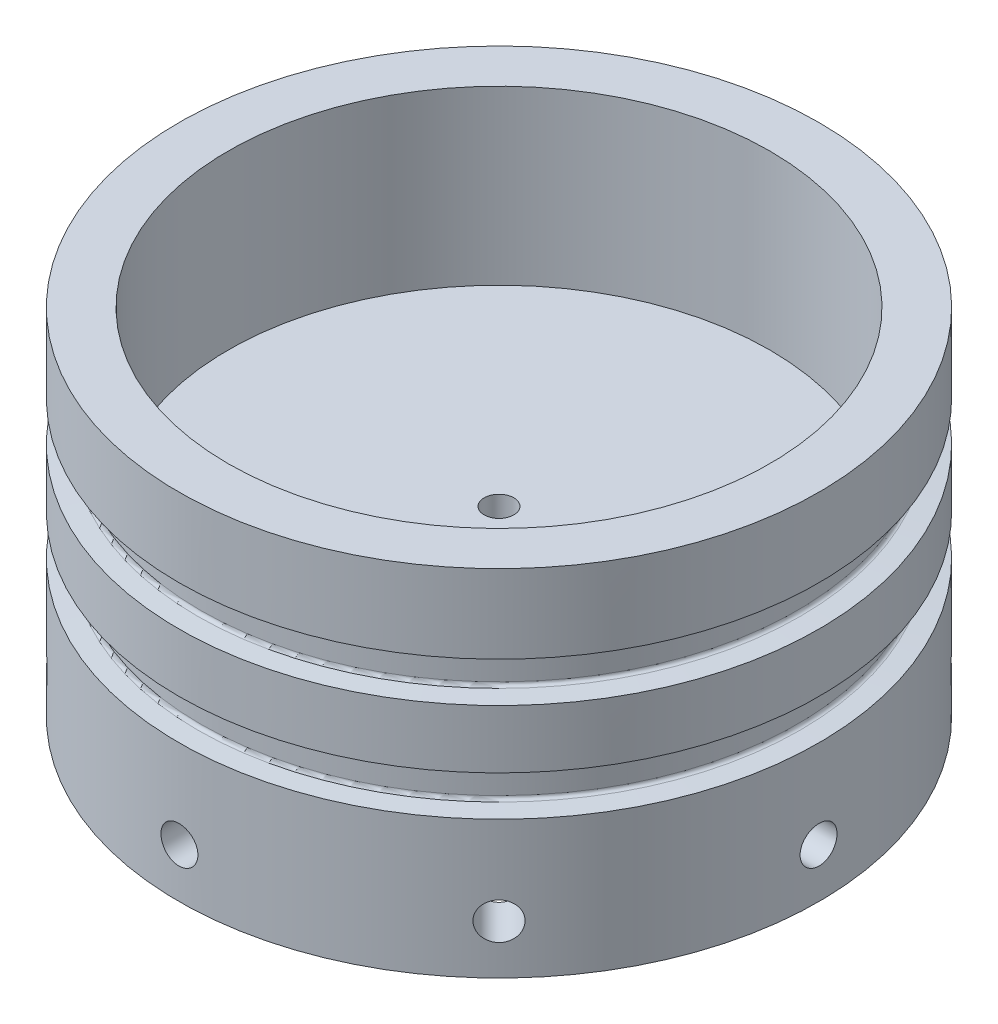
SolidWorks part; units mm, degrees
material "1060 Alloy"
ref_plane "Front Plane" through (0, 0, 0) normal (0, 0, 1) x (1, 0, 0)
ref_plane "Top Plane" through (0, 0, 0) normal (0, 1, 0) x (1, 0, 0)
ref_plane "Right Plane" through (0, 0, 0) normal (1, 0, 0) x (0, 0, -1)
sketch "Sketch1" plane through (0, 0, 0) normal (0, 0, 1) x (1, 0, 0)
  line L0 (0, 0) -> (0, 25.4) construction
  line L1 (-41.275, 13.97) -> (-41.275, 45.72)
  line L2 (-34.925, 13.97) -> (-5.1435, 13.97)
  line L3 (-1.9133, 0) -> (-1.9133, 23.495)
  line L4 (-1.9133, 23.495) -> (-34.925, 23.495)
  line L5 (-34.925, 23.495) -> (-34.925, 45.72)
  line L6 (-34.925, 45.72) -> (-41.275, 45.72)
  line L7 (-41.275, 13.97) -> (-41.275, 0)
  line L8 (-1.9133, 0) -> (-5.1435, 0)
  line L9 (-5.1435, 0) -> (-5.1435, 13.97)
  line L10 (-41.275, 0) -> (-34.925, 0)
  line L11 (55, 0) -> (-55, 0) construction
  line L12 (-34.925, 0) -> (-34.925, 13.97)
  point P6 (-41.275, 13.97)
  point P17 (0, 0)
  dimension "D1" = 1.9133
  dimension "D2" = 34.925
  dimension "D3" = 31.75
  dimension "D4" = 6.35
  dimension "D5" = 9.525
  dimension "D6" = 13.97
  dimension "D7" = 5.1435
revolve "Revolve1" add sketch "Sketch1" angle 360 about L0
ref_plane "Plane1" through (0, 0, 0) normal (-1, 0, 0) x (0, 0, -1)
ref_plane "Plane2" through (0, 0, 0) normal (-1, 0, 0) x (0, 0, -1)
ref_plane "Plane3" through (0, 0, 0) normal (-1, 0, 0) x (0, 0, -1)
ref_plane "Plane4" through (0, 0, 0) normal (-1, 0, 0) x (0, 0, -1)
ref_plane "Plane5" through (0, 0, 0) normal (-1, 0, 0) x (0, 0, -1)
ref_plane "Plane6" through (0, 0, 0) normal (-1, 0, 0) x (0, 0, -1)
ref_plane "Plane7" through (0, 0, 0) normal (-1, 0, 0) x (0, 0, -1)
ref_plane "Plane8" through (0, 0, 0) normal (-1, 0, 0) x (0, 0, -1)
ref_plane "Plane9" through (0, 0, 0) normal (-1, 0, 0) x (0, 0, -1)
ref_plane "Plane10" through (0, 0, 0) normal (-1, 0, 0) x (0, 0, -1)
ref_plane "Plane11" through (0, 0, 0) normal (-1, 0, 0) x (0, 0, -1)
sketch "Sketch3" plane through (0, 0, 0) normal (-1, 0, 0) x (0, 0, -1)
  line L0 (38.8614, -30.6451) -> (41.3639, -30.4262)
  line L1 (41.3639, -30.4262) -> (41.3639, -35.6138)
  line L2 (41.3639, -35.6138) -> (38.8614, -35.3949)
  line L3 (38.4556, -34.9521) -> (38.4556, -31.0879)
  line L4 (0, 50) -> (0, -50) construction
  line L5 (-41.275, -45.72) -> (41.275, -45.72) construction
  arc A0 (38.8614, -35.3949) -> (38.4556, -34.9521) centre (38.9001, -34.9521) cw
  arc A1 (38.4556, -31.0879) -> (38.8614, -30.6451) centre (38.9001, -31.0879) cw
  point P11 (41.3639, -33.02)
  dimension "D4" = 0.4445
  dimension "D5" = 0.4445
  dimension "D10" = 12.7
  dimension "D1" = 5.1877
  dimension "D2" = 2.5025
  dimension "D3" = 3.8642
  dimension "D6" = 2.5025
  dimension "D7" = 85
  dimension "D8" = 85
  dimension "D9" = 95
revolve "Groove for AS 568-234, O-Ring1" cut sketch "Sketch3"
pattern_linear "LPattern1" count 2 spacing 12.7 along (0, -1, 0) of "Groove for AS 568-234, O-Ring1"
ref_plane "Plane12" through (0, 6.35, 0) normal (0, -1, 0) x (-1, 0, 0)
ref_axis "Axis1" through (0, 6.35, 45.4025) along (0, 0, -1)
hole_wizard "3/16 (0.1875) Diameter Hole1" positions "3DSketch2" profile "Sketch5" hole size "3/16" standard "ANSI Inch" end condition up to next
sketch3d "3DSketch2"
  line L1 (0, 6.35, 45.4025) -> (0, 6.35, -45.4025) construction
  point P4 (0, 6.35, -41.275)
  point P7 (0, 0, 0)
  point P8 (0, 0, 0)
  point P9 (0, 0, 0)
sketch "Sketch5" plane through (0, 6.35, -41.275) normal (1, 0, 0) x (0, 1, 0)
  line L0 (0, 0) -> (0, 6.35)
  line L1 (0, 6.35) -> (2.3812, 6.35)
  line L2 (2.3812, 6.35) -> (2.3812, 0)
  line L5 (2.3812, 0) -> (0, 0)
  line L11 (0, -6.35) -> (0, 107.95) construction
  dimension "Thru Hole Dia." = 4.7625
  dimension "Thru Hole Depth" = 6.35
ref_axis "Axis2" through (0, -2.286, 0) along (0, 1, 0)
pattern_circular "CirPattern1" count 8 over 360 about axis through (0, -2.286, 0) along (0, 1, 0) of "3/16 (0.1875) Diameter Hole1"
